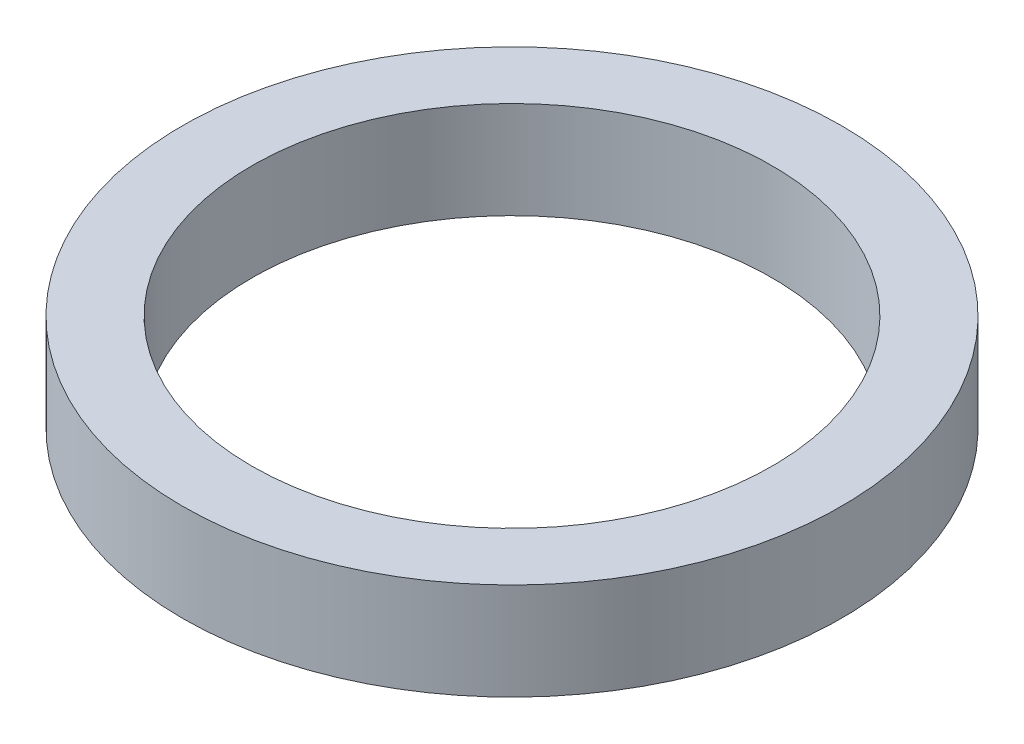
SolidWorks part; units mm, degrees
ref_plane "Front Plane" through (0, 0, 0) normal (0, 0, 1) x (1, 0, 0)
ref_plane "Top Plane" through (0, 0, 0) normal (0, 1, 0) x (1, 0, 0)
ref_plane "Right Plane" through (0, 0, 0) normal (1, 0, 0) x (0, 0, -1)
sketch "Sketch1" plane through (0, 0, 0) normal (0, 1, 0) x (1, 0, 0)
  circle A0 centre (0, 0) radius 47.5
  dimension "FLANGE_OD" = 95
extrude "Boss-Extrude1" add sketch "Sketch1" along normal blind 14
sketch "Sketch2" plane through (0, 0, 0) normal (0, 1, 0) x (1, 0, 0)
  circle A0 centre (0, 0) radius 37.5
  dimension "BORE_D" = 75
extrude "Cut-Extrude1" cut sketch "Sketch2" along normal through all
sketch "Sketch3" plane through (0, 14, 0) normal (0, 1, 0) x (1, 0, 0)
  circle A0 centre (0, 0) radius 20.9174 construction
  circle A1 centre (-20.9174, 0) radius 1.7186
  dimension "BOLT_D" = 3.4372
  dimension "BOLT_PCD" = 41.8348
extrude "Cut-Extrude2" cut sketch "Sketch3" against normal blind 11.2857 rebuild error yes
pattern_circular "CirPattern1" count 6 over 360 rebuild error yes
